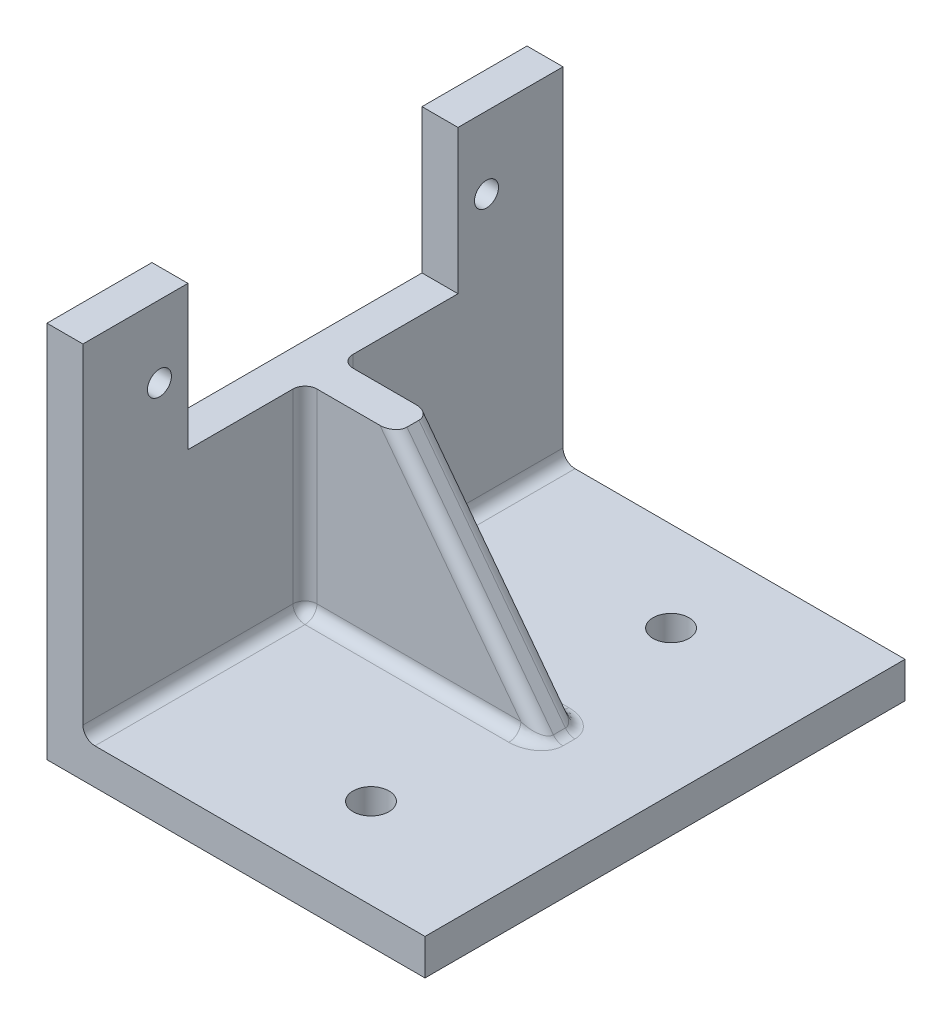
SolidWorks part; units mm, degrees
ref_plane "Front Plane" through (0, 0, 0) normal (0, 0, 1) x (1, 0, 0)
ref_plane "Top Plane" through (0, 0, 0) normal (0, 1, 0) x (1, 0, 0)
ref_plane "Right Plane" through (0, 0, 0) normal (1, 0, 0) x (0, 0, -1)
sketch "Sketch3" plane through (0, 0, 0) normal (0, 0, 1) x (1, 0, 0)
  line L0 (0, 30) -> (0, 0)
  line L1 (0, 0) -> (30, 0)
  dimension "D1" = 30
  dimension "D2" = 30
extrude "Extrude-Thin1" add sketch "Sketch3" along normal mid plane 40 thin thin type mid plane wall 3
sketch "Sketch4" plane through (-1.5, 0, 0) normal (-1, 0, 0) x (0, 0, 1)
  line L0 (0, 0) -> (0, 30) construction
  line L1 (20, 30) -> (-20, 30) construction
  line L2 (-20, 24) -> (20, 24) construction
  line L3 (-11.25, 30) -> (11.25, 30)
  line L4 (-11.25, 30) -> (-11.25, 18)
  line L5 (-11.25, 18) -> (11.25, 18)
  line L6 (11.25, 30) -> (11.25, 18)
  line L7 (-20, 30) -> (-20, -1.5) construction
  line L8 (20, 30) -> (20, -1.5) construction
  circle A0 centre (-13.625, 24) radius 1
  circle A1 centre (13.625, 24) radius 1
  dimension "D3" = 27.25
  dimension "D4" = 2
  dimension "D1" = 22.5
  dimension "D2" = 12
extrude "Cut-Extrude1" cut sketch "Sketch4" against normal through all
sketch "Sketch5" plane through (0, 1.5, 0) normal (0, 1, 0) x (1, 0, 0)
  line L0 (0, 0) -> (30, 0) construction
  line L1 (30, -20) -> (30, 20) construction
  circle A0 centre (18, -12.5) radius 1.5
  circle A1 centre (18, 12.5) radius 1.5
  dimension "D1" = 3
  dimension "D2" = 12
  dimension "D3" = 25
extrude "Cut-Extrude2" cut sketch "Sketch5" against normal through all
sketch "Sketch6" plane through (1.5, 0, 0) normal (1, 0, 0) x (0, 0, -1)
  line L0 (0, 0) -> (0, 18) construction
  line L1 (-11.25, 18) -> (11.25, 18) construction
  line L2 (-20, 1.5) -> (20, 1.5) construction
  line L3 (-1.5, 18) -> (1.5, 18)
  line L4 (-1.5, 18) -> (-1.5, 1.5)
  line L5 (-1.5, 1.5) -> (1.5, 1.5)
  line L6 (1.5, 18) -> (1.5, 1.5)
  dimension "D1" = 3
extrude "Boss-Extrude1" add sketch "Sketch6" along normal blind 20
sketch "Sketch7" plane through (0, 0, 1.5) normal (0, 0, 1) x (1, 0, 0)
  line L0 (9, 18) -> (21.5, 1.5)
  line L1 (21.5, 18) -> (1.5, 18) construction
  line L2 (1.5, 30) -> (1.5, 1.5) construction
  line L3 (9, 18) -> (21.5, 18)
  line L4 (21.5, 18) -> (21.5, 1.5)
  dimension "D1" = 7.5
extrude "Cut-Extrude3" cut sketch "Sketch7" against normal through all
fillet "Fillet1" radius 1 9 edges at (11.5, 1.5, 1.5) (11.5, 1.5, -1.5) (1.5, 1.5, -10.75) (1.5, 9.75, -1.5) (1.5, 9.75, 1.5) (1.5, 1.5, 10.75) (21.5, 1.5, 0) (15.25, 9.75, -1.5) (15.25, 9.75, 1.5)
